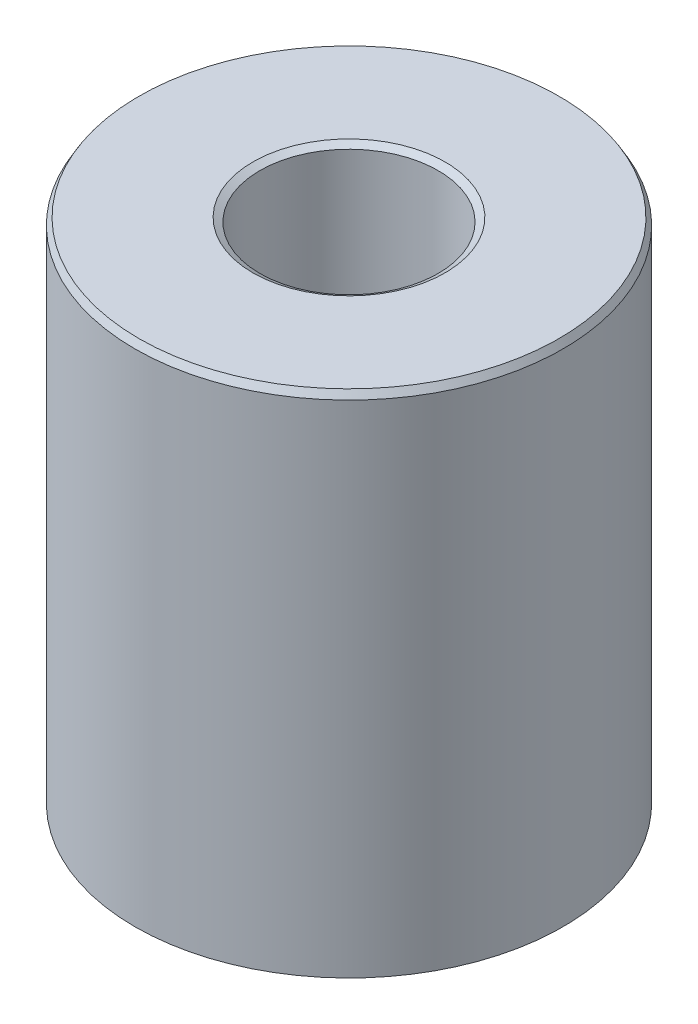
SolidWorks part; units mm, degrees
ref_plane "Front Plane" through (0, 0, 0) normal (0, 0, 1) x (1, 0, 0)
ref_plane "Top Plane" through (0, 0, 0) normal (0, 1, 0) x (1, 0, 0)
ref_plane "Right Plane" through (0, 0, 0) normal (1, 0, 0) x (0, 0, -1)
sketch "Sketch1" plane through (0, 0, 0) normal (0, 1, 0) x (1, 0, 0)
  circle A0 centre (0, 0) radius 42.5
  dimension "SLEEVE_OD" = 85
extrude "Boss-Extrude1" add sketch "Sketch1" along normal blind 101.5683
sketch "Sketch2" plane through (0, 0, 0) normal (0, 1, 0) x (1, 0, 0)
  circle A0 centre (0, 0) radius 17.7093
  dimension "BORE_D" = 35.4185
extrude "Cut-Extrude1" cut sketch "Sketch2" along normal through all
chamfer "Chamfer1" distance 1.3793 angle 30 4 edges at (0, 101.5683, 17.7093) (0, 0, 17.7093) (0, 0, 42.5) (0, 101.5683, 42.5) first distance on face at (0, 101.5683, 17.7093) first distance on face at (0, 0, 17.7093) first distance on face at (0, 101.5683, 42.5)
